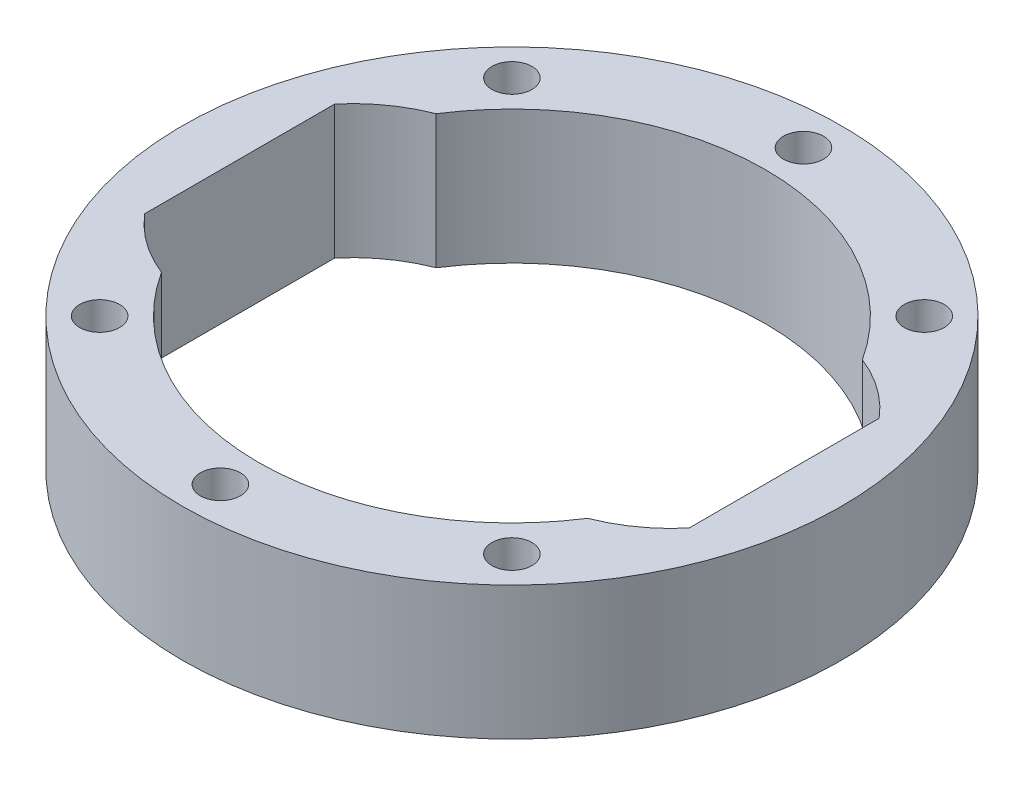
SolidWorks part; units mm, degrees
ref_plane "Front Plane" through (0, 0, 0) normal (0, 0, 1) x (1, 0, 0)
ref_plane "Top Plane" through (0, 0, 0) normal (0, 1, 0) x (1, 0, 0)
ref_plane "Right Plane" through (0, 0, 0) normal (1, 0, 0) x (0, 0, -1)
sketch "Sketch2" plane through (0, 0, 0) normal (0, 1, 0) x (1, 0, 0)
  line L5 (-40.8, 14.2408) -> (-40.8, -14.2408)
  line L9 (40.8, 14.2408) -> (40.8, -14.2408)
  circle A0 centre (0, 0) radius 49.4
  arc A2 (-40.8, -14.2408) -> (-31.9414, -20.5851) centre (-23.9, 0) ccw
  arc A3 (31.9414, -20.5851) -> (40.8, -14.2408) centre (23.9, 0) ccw
  arc A4 (-31.9414, 20.5851) -> (-40.8, 14.2408) centre (-23.9, 0) ccw
  arc A7 (40.8, 14.2408) -> (31.9414, 20.5851) centre (23.9, 0) ccw
  arc A18 (-31.9414, -20.5851) -> (31.9414, -20.5851) centre (0, 0) ccw
  arc A22 (31.9414, 20.5851) -> (-31.9414, 20.5851) centre (0, 0) ccw
  circle A23 centre (0, 43.7) radius 3
  circle A24 centre (30.9006, 30.9006) radius 3
  circle A26 centre (30.9006, -30.9006) radius 3
  circle A27 centre (0, -43.7) radius 3
  circle A28 centre (-30.9006, -30.9006) radius 3
  circle A30 centre (-30.9006, 30.9006) radius 3
  arc A31 (40.8, 0.7681) -> (40.8, -0.7681) centre (43.7, 0) ccw [skipped]
  arc A32 (-40.8, -0.7681) -> (-40.8, 0.7681) centre (-43.7, 0) ccw [skipped]
  point P30 (0, 0)
  dimension "D1" = 98.8
  dimension "D2" = 6
  dimension "D4" = 8
  dimension "D3" = 43.7
extrude "Boss-Extrude1" add sketch "Sketch2" along normal blind 20 contours A4 L5 A2 A18 A3 L9 A7 A22 | A0
extrude "Cut-Extrude1" cut sketch "Sketch2<9>" along normal blind 20 contours A23 | A24 | A26 | A27 | A28 | A30
sketch "Sketch2<9>" plane through (0, 0, 0) normal (0, 1, 0) x (1, 0, 0) same geometry as "Sketch2"
